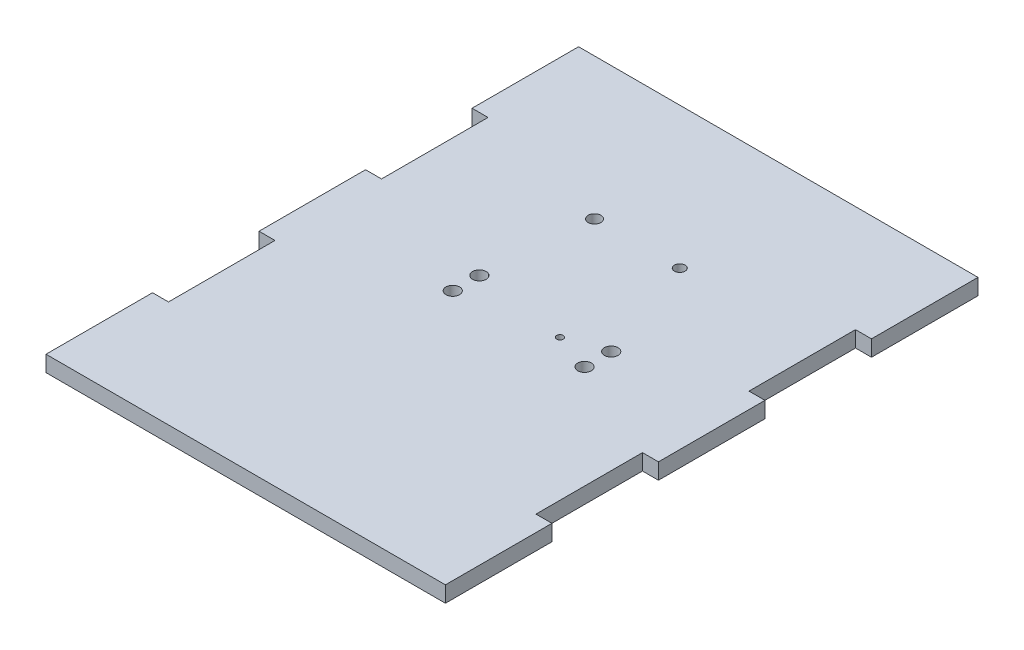
SolidWorks part; units mm, degrees
material "Pine"
ref_plane "Front Plane" through (0, 0, 0) normal (0, 0, 1) x (1, 0, 0)
ref_plane "Top Plane" through (0, 0, 0) normal (0, 1, 0) x (1, 0, 0)
ref_plane "Right Plane" through (0, 0, 0) normal (1, 0, 0) x (0, 0, -1)
sketch "Sketch1" plane through (0, 0, 0) normal (0, 1, 0) x (1, 0, 0)
  line L1 (-75, 100) -> (75, 100)
  line L2 (-75, 100) -> (-75, -100)
  line L3 (-75, -100) -> (75, -100)
  line L4 (75, 100) -> (75, -100)
  line L5 (-75, 100) -> (75, -100) construction
  line L6 (-75, -100) -> (75, 100) construction
  point P0 (0, 0)
  dimension "D1" = 150
  dimension "D2" = 200
extrude "Boss-Extrude1" add sketch "Sketch1" along normal blind 6
sketch "Sketch2" plane through (0, 6, 0) normal (0, 1, 0) x (1, 0, 0)
  line L0 (-75, 100) -> (-75, -100) construction
  line L1 (-75, 60) -> (-69, 60)
  line L2 (-75, 60) -> (-75, 20)
  line L3 (-75, 20) -> (-69, 20)
  line L4 (-69, 60) -> (-69, 20)
  line L5 (75, 100) -> (-75, 100) construction
  line L6 (69, 60) -> (69, 20)
  line L7 (69, 60) -> (75, 60)
  line L8 (75, 60) -> (75, 20)
  line L9 (69, 20) -> (75, 20)
  line L10 (69, -20) -> (69, -60)
  line L11 (69, -20) -> (75, -20)
  line L12 (75, -20) -> (75, -60)
  line L13 (69, -60) -> (75, -60)
  line L14 (-75, -20) -> (-75, -60)
  line L15 (-75, -20) -> (-69, -20)
  line L16 (-69, -20) -> (-69, -60)
  line L17 (-75, -60) -> (-69, -60)
  dimension "D1" = 40
  dimension "D2" = 40
  dimension "D3" = 6
  dimension "D4" = 2
  dimension "D5" = 2
extrude "Cut-Extrude1" cut sketch "Sketch2" against normal blind 6
sketch "Sketch6" plane through (0, 6, 0) normal (0, 1, 0) x (1, 0, 0)
  line L1 (75, -100) -> (75, -60) construction
  circle A0 centre (16, 2) radius 1.23
  dimension "D1" = 2.46
  dimension "D2" = 102
  dimension "D3" = 59
extrude "Cut-Extrude6" cut sketch "Sketch6" against normal through all
sketch "Sketch7" plane through (0, 6, 0) normal (0, 1, 0) x (1, 0, 0)
  line L0 (75, -100) -> (75, -60) construction
  line L1 (-75, -100) -> (75, -100) construction
  circle A0 centre (16, 47) radius 2
  dimension "D1" = 59
  dimension "D2" = 147
extrude "Cut-Extrude7" cut sketch "Sketch7" against normal through all
sketch "Sketch8" plane through (0, 6, 0) normal (0, 1, 0) x (1, 0, 0)
  line L0 (75, 60) -> (75, 100) construction
  line L1 (-75, -100) -> (75, -100) construction
  circle A0 centre (-16, 47) radius 2.38
  dimension "D1" = 91
  dimension "D2" = 147
extrude "Cut-Extrude8" cut sketch "Sketch8" against normal through all
sketch "Sketch9" plane through (0, 6, 0) normal (0, 1, 0) x (1, 0, 0)
  circle A0 centre (30.25, 7) radius 2.55
  circle A1 centre (30.25, -3) radius 2.55
  circle A2 centre (-19.25, 7) radius 2.55
  circle A3 centre (-19.25, -3) radius 2.55
  point P8 (0, 0)
  point P10 (0, 0)
  dimension "D1" = 49.5
  dimension "D2" = 0
  dimension "D3" = 10
  dimension "D4" = 0
  dimension "D5" = 49.5
  dimension "D6" = 0
  dimension "D7" = 93
  dimension "D8" = 55.75
extrude "Cut-Extrude9" cut sketch "Sketch9" against normal through all
